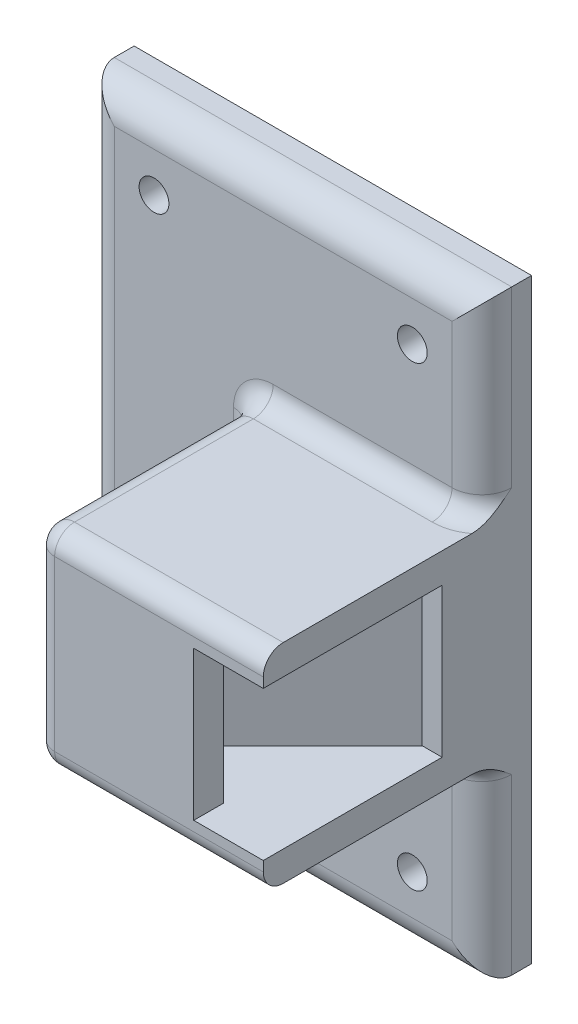
SolidWorks part; units mm, degrees
ref_plane "Front Plane" through (0, 0, 0) normal (0, 0, 1) x (1, 0, 0)
ref_plane "Top Plane" through (0, 0, 0) normal (0, 1, 0) x (1, 0, 0)
ref_plane "Right Plane" through (0, 0, 0) normal (1, 0, 0) x (0, 0, -1)
sketch "Sketch1" plane through (0, 0, 0) normal (0, 0, 1) x (1, 0, 0)
  line L1 (-18.1159, 13.5507) -> (21.8841, 13.5507)
  line L2 (-18.1159, 13.5507) -> (-18.1159, -46.4493)
  line L3 (-18.1159, -46.4493) -> (21.8841, -46.4493)
  line L4 (21.8841, 13.5507) -> (21.8841, -46.4493)
  circle A0 centre (14.8841, 6.5507) radius 1.5
  circle A1 centre (14.8841, -39.4493) radius 1.5
  circle A2 centre (-11.1159, -39.4493) radius 1.5
  circle A3 centre (-11.1159, 6.5507) radius 1.5
  dimension "D3" = 3
  dimension "D1" = 40
  dimension "D2" = 60
  dimension "D4" = 7
  dimension "D5" = 7
extrude "Boss-Extrude1" add sketch "Sketch1" along normal blind 5
sketch "Sketch3" plane through (0, 0, 5) normal (0, 0, 1) x (1, 0, 0)
  line L0 (10.3841, -5.9493) -> (10.3841, 13.5507)
  line L1 (-1.1159, -5.9493) -> (21.8841, -5.9493)
  line L2 (-1.1159, -5.9493) -> (-1.1159, -26.9493)
  line L3 (-1.1159, -26.9493) -> (21.8841, -26.9493)
  line L4 (21.8841, -5.9493) -> (21.8841, -26.9493)
  line L5 (21.8841, 13.5507) -> (-18.1159, 13.5507) construction
  line L6 (10.3841, -26.9493) -> (10.3841, -46.4493)
  line L7 (-18.1159, -46.4493) -> (21.8841, -46.4493) construction
  line L8 (21.8841, -46.4493) -> (21.8841, 13.5507) construction
  dimension "D1" = 23
  dimension "D2" = 21
  dimension "D3" = 0
extrude "Boss-Extrude2" add sketch "Sketch3" along normal blind 22 contours L4 L1 L2 L3 region at (10.3841, -16.4493, 5)
sketch "Sketch4" plane through (0, -26.9493, 0) normal (0, -1, 0) x (1, 0, 0)
  line L0 (4.8841, 24) -> (19.8841, 9)
  line L1 (19.8841, 24) -> (4.8841, 24)
  line L2 (19.8841, 24) -> (19.8841, 9)
  line L3 (19.8841, 9) -> (4.8841, 9)
  line L4 (4.8841, 24) -> (4.8841, 9)
  line L5 (-18.1159, 5) -> (21.8841, 5) construction
  line L6 (21.8841, 27) -> (21.8841, 5) construction
  line L7 (21.8841, 27) -> (14.8841, 27)
  line L8 (19.8841, 24) -> (21.8841, 24)
  line L9 (19.8841, 24) -> (19.8841, 9)
  line L10 (19.8841, 9) -> (21.8841, 9)
  line L11 (21.8841, 24) -> (21.8841, 9)
  line L12 (21.8841, 27) -> (21.8841, 5)
  line L13 (21.8841, 5) -> (14.8841, 5)
  line L14 (14.8841, 27) -> (14.8841, 5)
  line L15 (-1.1159, 5) -> (21.8841, 5) construction
  line M6 (21.8841, 5) -> (21.8841, 27)
  line M7 (21.8841, 27) -> (-1.1159, 27)
  dimension "D1" = 15
  dimension "D2" = 2
  dimension "D3" = 7
  dimension "D4" = 4
extrude "Cut-Extrude1" cut sketch "Sketch4" against normal blind 15 from offset 3 contours L2 L10 L8 M6 | L1 L14 L0 L2 | L14 L1 L8 M7 M6 | L14 L1 L0 region at (11.5507, -26.9493, 20.6667) region at (17.5507, -26.9493, 17.6667) region at (18.3841, -26.9493, 25.5) region at (20.8841, -26.9493, 16.5) offset against normal yes
fillet "Fillet1" radius 3 5 edges at (21.8841, 3.8007, 5) (1.8841, 13.5507, 5) (-18.1159, -16.4493, 5) (21.8841, -36.6993, 5) (1.8841, -46.4493, 5)
fillet "Fillet2" radius 2 10 edges at (21.0054, -5.9493, 4.1213) (21.0054, -26.9493, 4.1213) (-1.1159, -5.9493, 16) (8.8841, -5.9493, 5) (10.3841, -5.9493, 27) (-1.1159, -16.4493, 27) (-1.1159, -16.4493, 5) (8.8841, -26.9493, 5) (-1.1159, -26.9493, 16) (10.3841, -26.9493, 27)
